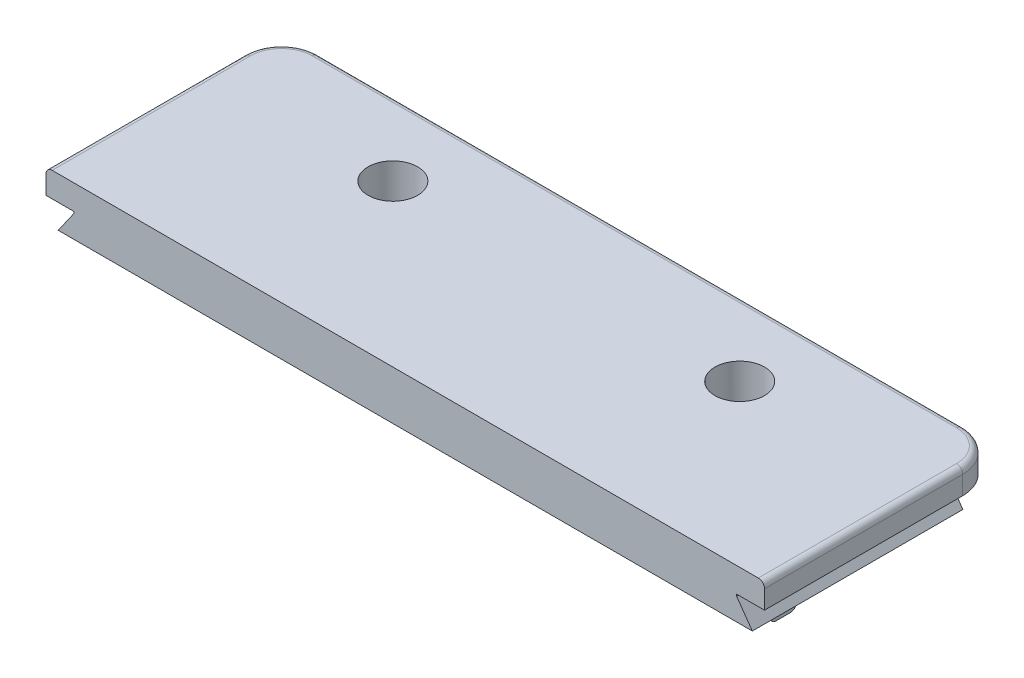
SolidWorks part; units mm, degrees
ref_plane "Front Plane" through (0, 0, 0) normal (0, 0, 1) x (1, 0, 0)
ref_plane "Top Plane" through (0, 0, 0) normal (0, 1, 0) x (1, 0, 0)
ref_plane "Right Plane" through (0, 0, 0) normal (1, 0, 0) x (0, 0, -1)
sketch "Sketch1" plane through (0, 0, 0) normal (0, 0, 1) x (1, 0, 0)
  line L0 (-29, 29) -> (-27, 29) construction
  line L1 (-29, 29) -> (-27, 29) construction
  line L2 (27, 29) -> (29, 29) construction
  line L3 (27, 29) -> (29, 29) construction
  line L4 (-27, 29) -> (-28.4004, 27)
  line L5 (-28.4004, 27) -> (28.4004, 27)
  line L6 (28.4004, 27) -> (27, 29)
  line L7 (27, 29) -> (-27, 29)
  line L8 (-27, 29) -> (-28.4004, 27) construction
  line L9 (-28.4004, 27) -> (28.4004, 27) construction
  line L10 (28.4004, 27) -> (27, 29) construction
  line L11 (27, 29) -> (-27, 29) construction
  line L12 (-26.7558, 29) -> (-28.0162, 27.2)
  line L13 (-28.0162, 27.2) -> (28.0162, 27.2)
  line L14 (28.0162, 27.2) -> (26.7558, 29)
  line L15 (-26.8362, 28.8853) -> (-28.0162, 27.2) construction
  line L16 (28.0162, 27.2) -> (26.8362, 28.8853) construction
  line L17 (26.7558, 29) -> (-26.7558, 29) construction
  line L18 (-26.7558, 29) -> (-26.7558, 29.15)
  line L19 (-26.7558, 29.15) -> (-29, 29.15)
  line L20 (-29, 29.15) -> (-29, 31.15)
  line L21 (0, 29) -> (0, 0.5) construction
  line L22 (0, 31.15) -> (0, 0.5) construction
  line L23 (-29, 31.15) -> (29, 31.15)
  line L24 (-29, 29) -> (-29, 0.5) construction
  line L25 (29, 29.15) -> (29, 31.15)
  line L26 (26.7558, 29.15) -> (29, 29.15)
  line L27 (26.7558, 29) -> (26.7558, 29.15)
  line L28 (27, 29) -> (-27, 29) construction
  dimension "D3" = 0.15
  dimension "D4" = 2
  dimension "D1" = 0
  dimension "D2" = 0.2
extrude "Boss-Extrude1" add sketch "Sketch1" against normal up to surface (17 mm away)
sketch "Sketch3" plane through (0, 0, -17) normal (0, 0, -1) x (-1, 0, 0)
  line L1 (-29, 31.15) -> (29, 31.15)
  line L2 (-29, 31.15) -> (-29, 29.15)
  line L3 (-29, 29.15) -> (29, 29.15)
  line L4 (29, 31.15) -> (29, 29.15)
extrude "Boss-Extrude2" add sketch "Sketch3" along normal up to surface (2 mm away)
fillet "Fillet1" radius 3 2 edges at (29, 30.15, -19) (-29, 30.15, -19)
sketch "Sketch4" plane through (0, 27.2, 0) normal (0, -1, 0) x (1, 0, 0)
  line L0 (28.0162, -17) -> (28.0162, 0) construction
  line L1 (28.0162, -1.5) -> (-28.0162, -1.5)
  line L2 (28.0162, -1.5) -> (28.0162, -3.5)
  line L3 (28.0162, -3.5) -> (-28.0162, -3.5)
  line L4 (-28.0162, -1.5) -> (-28.0162, -3.5)
  line L5 (-28.0162, -17) -> (-28.0162, 0) construction
  line L6 (-28.0162, 0) -> (28.0162, 0) construction
  dimension "D1" = 2
  dimension "D2" = 1.5
extrude "Boss-Extrude3" add sketch "Sketch4" along normal blind 0.25
fillet "Fillet2" radius 0.5 2 edges at (0, 26.95, -3.5) (0, 26.95, -1.5)
sketch "Sketch7" plane through (0, 31.15, 0) normal (0, 1, 0) x (1, 0, 0)
  line L0 (29, 0) -> (-29, 0) construction
  line L1 (29, 16) -> (29, 0) construction
  line L2 (29, 13) -> (-29, 13) construction
  line L3 (-12, 13) -> (12, 13) construction
  line L4 (0, 0) -> (0, 19) construction
  line L5 (26, 19) -> (-26, 19) construction
  line L7 (-14, 11) -> (14, 11) construction
  line L9 (-29, 16) -> (-29, 0) construction
  line L10 (-28.0162, 17) -> (28.0162, 17) construction
  circle A0 centre (14, 13) radius 2
  circle A3 centre (-14, 13) radius 2
  point P15 (-29, 12.2685)
  point P18 (29, 12.4317)
  dimension "D1" = 4
  dimension "D2" = 6
  dimension "D3" = 15
extrude "Cut-Extrude2" cut sketch "Sketch7" against normal up to next
fillet "Fillet3" radius 0.5 5 edges at (-29, 31.15, -8) (-28.1213, 31.15, -18.1213) (0, 31.15, -19) (28.1213, 31.15, -18.1213) (29, 31.15, -8)
